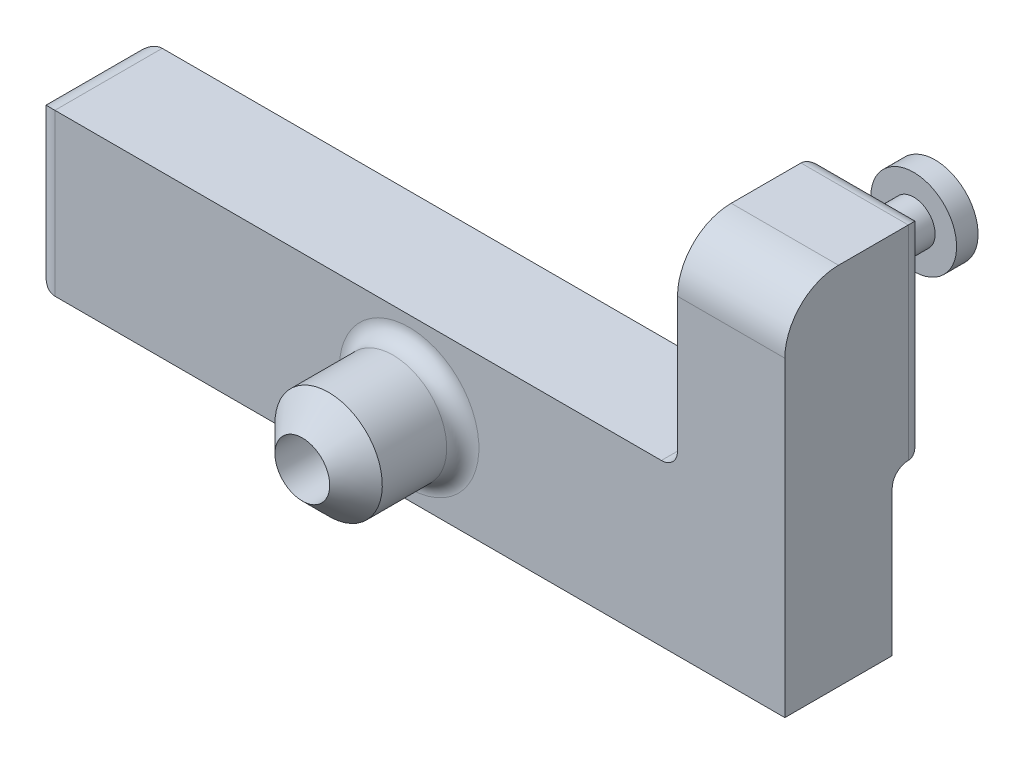
SolidWorks part; units mm, degrees
ref_plane "Front Plane" through (0, 0, 0) normal (0, 0, 1) x (1, 0, 0)
ref_plane "Top Plane" through (0, 0, 0) normal (0, 1, 0) x (1, 0, 0)
ref_plane "Right Plane" through (0, 0, 0) normal (1, 0, 0) x (0, 0, -1)
sketch "Sketch1" plane through (0, 0, 0) normal (0, 0, 1) x (1, 0, 0)
  line L0 (-35, -7.5) -> (35, -7.5)
  line L1 (-35, -7.5) -> (-35, 7.5)
  line L2 (35, -7.5) -> (35, 7.5)
  line L3 (-35, 7.5) -> (35, 7.5)
  line L4 (-35, -7.5) -> (35, 7.5) construction
  line L5 (35, -7.5) -> (-35, 7.5) construction
  circle A0 centre (0, 0) radius 2.55
  point P1 (0, 0)
  dimension "D3" = 5.1
  dimension "D1" = 70
  dimension "D2" = 15
  dimension "D4" = 35
extrude "Boss-Extrude1" add sketch "Sketch1" along normal blind 10
sketch "Sketch5" plane through (0, 0, 0) normal (0, 0, -1) x (-1, 0, 0)
  line L0 (-35, 26.5) -> (-25, 26.5)
  line L1 (-35, 26.5) -> (-35, 7.5)
  line L2 (-25, 26.5) -> (-25, 7.5)
  line L3 (-35, 7.5) -> (-25, 7.5)
  line L7 (-35, 7.5) -> (35, 7.5) construction
  line L8 (-35, -7.5) -> (-35, 7.5) construction
  dimension "D1" = 10
  dimension "D2" = 19
extrude "Boss-Extrude5" add sketch "Sketch5" against normal blind 10 and the other way blind 3 separate body
sketch "Sketch2" plane through (0, 0, 10) normal (0, 0, 1) x (1, 0, 0)
  line L0 (-35, 7.5) -> (-25, 7.5)
  line L1 (-35, 7.5) -> (-35, 17.5)
  line L2 (-25, 7.5) -> (-25, 17.5)
  line L3 (-35, 17.5) -> (-25, 17.5)
  line L4 (35, 7.5) -> (-35, 7.5) construction
  dimension "D1" = 10
  dimension "D2" = 10
extrude "Boss-Extrude2" [suppressed] add sketch "Sketch2" against normal blind 10
sketch "Sketch3" plane through (-35, 0, -3) normal (0, 0, -1) x (-1, 0, 0)
  line L0 (-70, -7.5) -> (-70, 7.5) construction
  line L1 (-60, 7.5) -> (-60, 26.5) construction
  line L2 (-60, 26.5) -> (-70, 26.5) construction
  circle A0 centre (-65, 21.5) radius 2
  point P9 (-60, 17)
  dimension "D1" = 4
  dimension "D2" = 5
  dimension "D3" = 5
fillet "Fillet1" radius 2 4 edges at (-35, 0, 0) (-35, -7.5, 5) (-35, 0, 10) (-35, 7.5, 5)
extrude "Boss-Extrude6" add sketch "Sketch3" along normal blind 4
sketch "Sketch6" plane through (0, 0, -7) normal (0, 0, -1) x (-1, 0, 0)
  circle A2 centre (-30, 21.5) radius 4
  circle A3 centre (-30, 21.5) radius 4
  dimension "D1" = 2
extrude "Boss-Extrude7" add sketch "Sketch6" along normal blind 2
fillet "Fillet4" radius 5 1 edges at (30, 26.5, 10)
combine bodies "Combine1" operation type add bodies to combine 106 105 107 101
fillet "Fillet7" [suppressed] radius 2
fillet "Fillet3" radius 1.5 5 edges at (30, 7.5, -3) (30, 7.5, 0) (25, 17, -3) (30, 26.5, -3) (35, 17, -3)
fillet "Fillet9" radius 1.5 2 edges at (25, 6.75, 0) (25, 7.5, 5)
sketch "Sketch8" plane through (0, 0, 0) normal (1, 0, 0) x (0, 0, -1)
  line L0 (-10, 0) -> (-20, 0)
  line L1 (-10, 21.5) -> (-10, -7.5) construction
  line L2 (-20, 0) -> (-20, 2.5)
  line L3 (-20, 2.5) -> (-17.5, 5)
  line L4 (-17.5, 5) -> (-10, 5)
  line L5 (-10, 5) -> (-10, 0)
  dimension "D1" = 2.5
  dimension "D2" = 5
  dimension "D3" = 10
  dimension "D4" = 135
revolve "Revolve1" add sketch "Sketch8" angle 360 about L0
sketch "Sketch9" plane through (0, 0, 10) normal (0, 0, -1) x (-1, 0, 0)
  circle A1 centre (0, 0) radius 2.55
  circle A2 centre (0, 0) radius 2.55
  dimension "D1" = 0
extrude "Cut-Extrude1" cut sketch "Sketch9" against normal blind 10
fillet "Fillet10" radius 1.5 1 edges at (0, 5, 10)
sketch "Sketch10" plane through (0, 0, 0) normal (0, 0, -1) x (-1, 0, 0)
  line L1 (33, -7.5) -> (-35, -7.5) construction
  line L2 (-35, -7.5) -> (-35, 6) construction
  line L3 (-35, -5.5) -> (-35, -7.5)
  line L4 (-35, -7.5) -> (-15, -7.5)
  arc A0 (-15, -7.5) -> (-35, -5.5) centre (-15, 93.5) cw
  point P10 (-35, 12.5)
  point P11 (0, 0)
  point P12 (-30, -0.4337)
  point P13 (0, 0)
  point P14 (-24.9016, -4.6775)
  point P15 (-35, -4.0751)
  point P16 (-35, -4.3708)
  point P17 (-34.1204, -4.3719)
  dimension "D2" = 2
  dimension "D1" = 20
extrude "Cut-Extrude2" [suppressed] cut sketch "Sketch10" against normal blind 10
